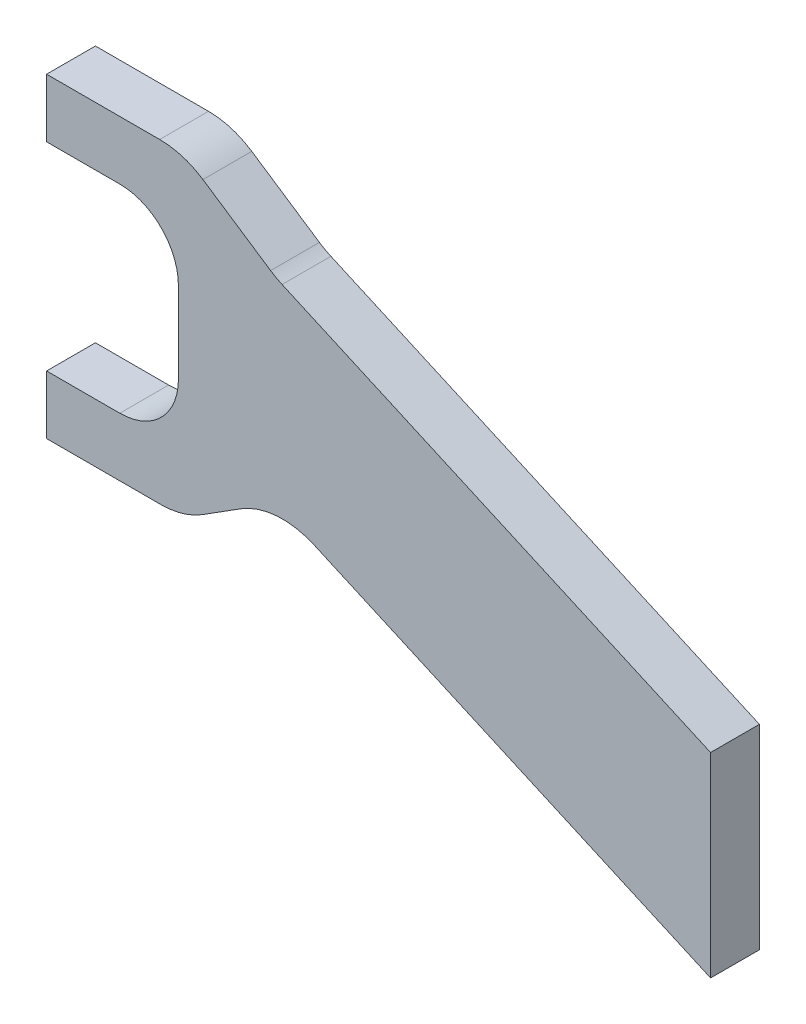
SolidWorks part; units mm, degrees
material "PBT General Purpose"
ref_plane "Front Plane" through (0, 0, 0) normal (0, 0, 1) x (1, 0, 0)
ref_plane "Top Plane" through (0, 0, 0) normal (0, 1, 0) x (1, 0, 0)
ref_plane "Right Plane" through (0, 0, 0) normal (1, 0, 0) x (0, 0, -1)
sketch "frame_outline" plane through (0, 0, 0) normal (0, 0, 1) x (1, 0, 0)
  line L89 (0, 1.616) -> (0, 1.316)
  line L99 (0, 1.316) -> (0.675, 1.316)
  line L100 (0.675, 1.316) -> (0.675, 0.3)
  line L101 (0.675, 0.3) -> (0, 0.3)
  line L102 (0, 0.3) -> (0, 0)
  line L103 (0, 0) -> (0.7, 0)
  line L104 (0.7, 0) -> (1.175, 0.3)
  line L105 (1.175, 0.3) -> (3.4, -0.692)
  line L106 (3.4, -0.692) -> (3.4, 0.308)
  line L107 (3.4, 0.308) -> (1.175, 1.3)
  line L108 (1.175, 1.3) -> (0.7, 1.616)
  line L109 (0.7, 1.616) -> (0, 1.616)
  line L110 (0.675, 0.808) -> (3.9765, 0.808) construction
  point P24 (3.4, -0.192)
  dimension "D1" = 0.3
  dimension "D2" = 0.3
  dimension "D9" = 1.616
  dimension "D10" = 0.675
  dimension "D11" = 1
  dimension "D12" = 1
  dimension "D14" = 0.7
  dimension "D15" = 0.7
  dimension "D16" = 0.5
  dimension "D3" = 3.4
extrude "Boss-Extrude1" add sketch "frame_outline" along normal mid plane 0.25
fillet "Fillet1" radius 0.3 2 edges at (0.675, 0.3, 0) (0.675, 1.316, 0)
fillet "Fillet2" radius 0.4 4 edges at (0.7, 0, 0) (1.175, 0.3, 0) (1.175, 1.3, 0) (0.7, 1.616, 0)
equation "\"t\"= 0.25'thickness of the sheets"
equation "\"t_cf\"= 0.115'thickness of single carbon fiber layer"
equation "\"t_kapton\"= 0.025'thickness of single Kapton flex layer"
equation "\"t_fr4\"= 0.1'thickness of FR4 with copper layer"
equation "\"joint_flex\"= 0.1'Width of flextures gap"
equation "\"joint_flex_eff\"= 0.02'Width of flecture after castelation"
equation "\"joint_fold\"= 0.2'Width of folding joints for 90deg fold"
equation "\"gap_tolerance\"= 0.002'Width to have interfecence fit between carbon fiber inserts"
equation "\"assemble_angle\"= 90'Angle of assembly parts"
equation "\"D1@Boss-Extrude1\"=\"t\""
equation "\"D10@frame_outline\"=\"t\"*1.5+0.3+0.1-\"joint_flex\""
equation "\"link_lift\"= 0.5'Actuation linkage amplification for the lift motion"
equation "\"link_swing\"= 0.45'Actuation linkage amplification for the swing motion"
equation "\"D9@frame_outline\"=0.3*4+0.4+\"gap_tolerance\"*8"
